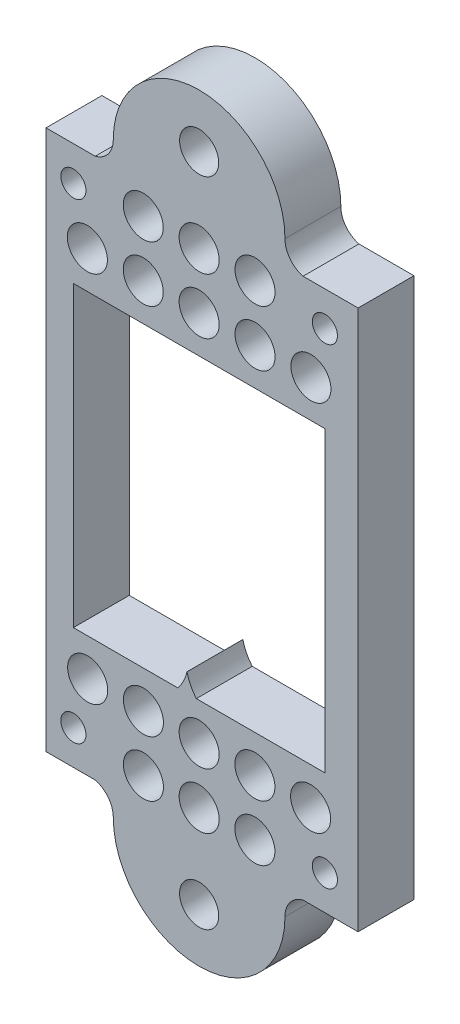
SolidWorks part; units mm, degrees
ref_plane "Front Plane" through (0, 0, 0) normal (0, 0, 1) x (1, 0, 0)
ref_plane "Top Plane" through (0, 0, 0) normal (0, 1, 0) x (1, 0, 0)
ref_plane "Right Plane" through (0, 0, 0) normal (1, 0, 0) x (0, 0, -1)
sketch "Sketch1" plane through (0, 0, 0) normal (0, 0, 1) x (1, 0, 0)
  line L0 (-13.5, -10.2592) -> (-1.3, -10.2592) construction
  line L1 (-16.4365, 29) -> (-11.1559, 29)
  line L2 (-16.4365, 29) -> (-16.4365, -29)
  line L3 (-16.4365, -29) -> (-11.1559, -29)
  line L4 (17.0635, 29) -> (17.0635, -29)
  line L5 (-13.5, 16) -> (13.5, 16)
  line L6 (-13.5, 16) -> (-13.5, -16)
  line L7 (-13.5, -16) -> (-2.3, -16)
  line L8 (13.5, 16) -> (13.5, -16)
  line L9 (-1.3, -10.2592) -> (-1.3, -16) construction
  line L10 (-2.3, -16) -> (-0.3, -16) construction
  line L12 (-0.3, -16) -> (13.5, -16)
  line L14 (-19.5, 29.3) -> (19.5, 29.3) construction
  line L15 (-19.5, 29.3) -> (-19.5, -29.3) construction
  line L16 (-19.5, -29.3) -> (19.5, -29.3) construction
  line L17 (19.5, 29.3) -> (19.5, -29.3) construction
  line L19 (-5, 27.5542) -> (5, 27.5542) construction
  line L20 (0, 0) -> (4.3335, 0) construction
  line L21 (11.1559, 29) -> (17.0635, 29)
  line L22 (11.1559, -29) -> (17.0635, -29)
  line L23 (0, 35) -> (0, 28.0589) construction
  circle A2 centre (-13.5, 25.3) radius 1.35
  circle A4 centre (13.5, -25.3) radius 1.35
  circle A5 centre (-13.5, -25.3) radius 1.35
  circle A6 centre (13.5, 25.3) radius 1.35
  arc A7 (-9.2149, 31.5247) -> (9.2149, 31.5247) centre (0, 31.5247) cw
  circle A8 centre (0, 35) radius 2.1
  circle A13 centre (0, -35) radius 2.1
  arc A16 (-9.2149, 31.5247) -> (-11.1559, 29) centre (-11.7911, 31.4968) cw
  arc A17 (9.2149, 31.5247) -> (11.1559, 29) centre (11.7911, 31.4968) ccw
  arc A21 (9.2149, -31.5247) -> (11.1559, -29) centre (11.7911, -31.4968) cw
  arc A22 (-9.2149, -31.5247) -> (-11.1559, -29) centre (-11.7911, -31.4968) ccw
  arc A23 (-9.2149, -31.5247) -> (9.2149, -31.5247) centre (0, -31.5247) ccw
  arc A24 (-2.3, -16) -> (-1.3, -14) centre (-5.8378, -12.9811) ccw
  arc A25 (-0.3, -16) -> (-1.3, -14) centre (3.2378, -12.9811) cw
  point P10 (-16.4365, 0)
  point P11 (0, 16)
  point P12 (-13.5, 0)
  point P16 (-1.3, -16)
  point P29 (19.5, 0)
  point P30 (0, 29.3)
  point P46 (0, 27.5542)
  dimension "D8" = 2.7
  dimension "D22" = 4.2
  dimension "D23" = 6
  dimension "D1" = 27
  dimension "D2" = 33.5
  dimension "D3" = 58
  dimension "D4" = 32
  dimension "D5" = 12.2
  dimension "D6" = 2
  dimension "D9" = 58.6
  dimension "D10" = 39
  dimension "D11" = 6
  dimension "D12" = 4
  dimension "D13" = 4
  dimension "D14" = 6
  dimension "D15" = 6
  dimension "D16" = 6
  dimension "D17" = 4
  dimension "D18" = 4
  dimension "D21" = 10
  dimension "D24" = 2
extrude "Boss-Extrude1" add sketch "Sketch1" along normal blind 6
sketch "Sketch2" plane through (0, 0, 6) normal (0, 0, 1) x (1, 0, 0)
  line L2 (-13.5, -16) -> (-2.3, -16) construction
  line L3 (13.5, 16) -> (-13.5, 16) construction
  circle A0 centre (-12, 20) radius 2.15
  circle A1 centre (-6, 20) radius 2.15
  circle A2 centre (0, 20) radius 2.15
  circle A3 centre (6, 20) radius 2.15
  circle A4 centre (12, 20) radius 2.15
  circle A5 centre (-6, 26) radius 2.15
  circle A6 centre (0, 26) radius 2.15
  circle A7 centre (6, 26) radius 2.15
  circle A8 centre (-11.9673, -20) radius 2.15
  circle A9 centre (-5.9837, -20) radius 2.15
  circle A10 centre (0, -20) radius 2.15
  circle A11 centre (5.9837, -20) radius 2.15
  circle A12 centre (11.9673, -20) radius 2.15
  circle A13 centre (-5.9837, -26) radius 2.15
  circle A14 centre (0, -26) radius 2.15
  circle A15 centre (5.9837, -26) radius 2.15
  dimension "D1" = 4.3
  dimension "D5" = 4.3
  dimension "D11" = 4.3
  dimension "D12" = 4.3
  dimension "D13" = 4.3
  dimension "D14" = 4.3
  dimension "D15" = 4.3
  dimension "D16" = 4.3
  dimension "D2" = 4
  dimension "D3" = 4
  dimension "D6" = 6
  dimension "D10" = 6
  dimension "D4" = 5
  dimension "D9" = 5
extrude "Cut-Extrude1" cut sketch "Sketch2" against normal blind 4.2
